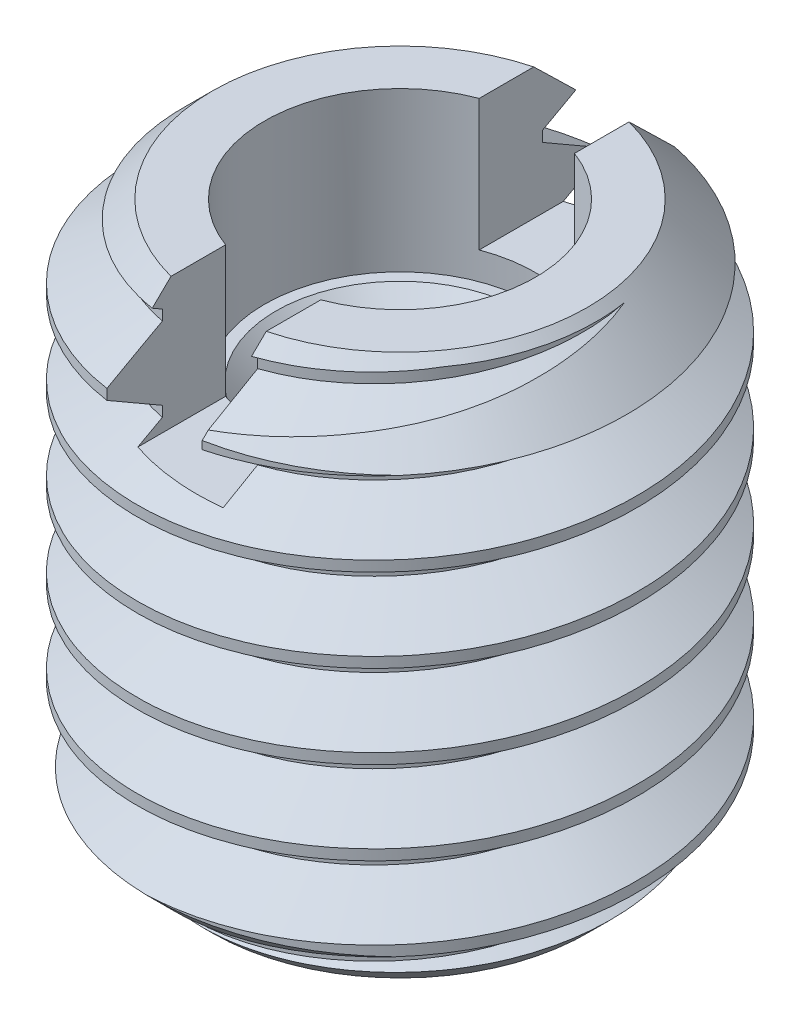
SolidWorks part; units mm, degrees
ref_plane "Front Plane" through (0, 0, 0) normal (0, 0, 1) x (1, 0, 0)
ref_plane "Top Plane" through (0, 0, 0) normal (0, 1, 0) x (1, 0, 0)
ref_plane "Right Plane" through (0, 0, 0) normal (1, 0, 0) x (0, 0, -1)
sketch "Sketch1" plane through (0, 0, 0) normal (0, 1, 0) x (1, 0, 0)
  line L0 (-3, 0) -> (3, 0) construction
  circle A0 centre (0, 0) radius 3
  dimension "External Thread OD" = 6
extrude "Extrude1" add sketch "Sketch1" against normal blind 6.5024
sketch "Sketch4" plane through (0, 0, 0) normal (0, 1, 0) x (1, 0, 0)
  circle A2 centre (0, 0) radius 1.5
  point P0 (-1.5, 0)
  dimension "Internal Thread OD" = 3
sketch "Sketch2" plane through (0, 0, 0) normal (0, 1, 0) x (1, 0, 0)
  circle A0 centre (0, 0) radius 1.6256
  dimension "A" = 3.2512
extrude "Extrude2" cut sketch "Sketch2" against normal blind 1.905
sketch "Sketch3" plane through (0, 0, 0) normal (0, 0, 1) x (1, 0, 0)
  line L5 (-0.5715, 0) -> (0.5715, 0)
  line L6 (-0.5715, 0) -> (-0.5715, -1.5748)
  line L7 (-0.5715, -1.5748) -> (0.5715, -1.5748)
  line L8 (0.5715, 0) -> (0.5715, -1.5748)
  dimension "B" = 1.143
  dimension "C" = 1.5748
extrude "Extrude3" cut sketch "Sketch3" along normal through all and the other way through all
curve "Helix/Spiral1" pitch 0.5 height 7.0024 radius 1.5 centre (0, 0, 0) axis (0, -1, 0) start towards (0, 0, 1) parameters "Internal Thread Height"=7.0024, "Internal Thread Pitch"=0.5
sketch "Sketch5" plane through (0, 0, 0) normal (0, 0, 1) x (1, 0, 0)
  line L0 (-1.1211, 0.4688) -> (-1.1211, -0.0312) construction
  line L1 (-1.1211, -0.0312) -> (-1.5541, 0.2188) construction
  line L2 (-1.5541, 0.2188) -> (-1.1211, 0.4688) construction
  line L3 (-1.1211, 0.2188) -> (-1.1752, 0.2188) construction
  line L4 (-1.1752, 0.2188) -> (-1.4459, 0.2188) construction
  line L5 (-1.5, 0.2188) -> (-1.5541, 0.2188) construction
  line L6 (-1.5, 0.25) -> (-1.5, 0.1875) construction
  line L7 (-1.1752, 0) -> (-1.1752, 0.4375) construction
  line L8 (-1.5, 0.1875) -> (-1.5, 0) construction
  line L9 (-1.5, 0) -> (-1.1752, 0) construction
  line L10 (-1.4459, 0.2813) -> (-1.4459, 0.1563)
  line L11 (-1.4459, 0.1563) -> (-1.1482, -0.0156)
  line L12 (-1.1482, -0.0156) -> (-1.1482, 0.4531)
  line L13 (-1.1482, 0.4531) -> (-1.4459, 0.2813)
  line L14 (-1.5, 0.2188) -> (-1.4459, 0.2188) construction
  point P18 (-1.1482, 0.2188)
  dimension "D1" = 0.5
  dimension "D2" = 0.0625
sketch "Sketch6" plane through (0, 0, 0) normal (0, 1, 0) x (-1, 0, 0)
  circle A0 centre (0, 0) radius 1.1752
extrude "Extrude4" cut sketch "Sketch6" against normal through all
chamfer "Chamfer1" distance 0.3125 angle 45 2 edges at (0, -6.5024, 1.1752) (0, -1.905, 1.1752)
sweep "Cut-Sweep1" cut profiles "Sketch5" path "Helix/Spiral1" align with end faces yes
sketch "Sketch7" plane through (0, 0, 0) normal (0, 1, 0) x (1, 0, 0)
  circle A0 centre (0, 0) radius 3 construction
  circle A1 centre (0, 0) radius 3
  point P3 (-3, 0)
curve "Helix/Spiral2" pitch 1 height 7.0024 radius 3 centre (0, 0, 0) axis (0, -1, 0) start towards (0, 0, 1) parameters "External Thread Height"=7.0024, "External Thread Pitch"=1
sketch "Sketch8" plane through (0, 0, 0) normal (0, 0, 1) x (1, 0, 0)
  line L0 (-3.1083, 0.9375) -> (-3.1083, -0.0625) construction
  line L1 (-3.1083, 0.9375) -> (-2.2422, 0.4375) construction
  line L2 (-2.2422, 0.4375) -> (-3.1083, -0.0625) construction
  line L3 (-3, 0.875) -> (-3, 0) construction
  line L4 (-2.3505, 0.5) -> (-2.3505, 0.375)
  line L5 (-3.0541, 0.9063) -> (-2.3505, 0.5)
  line L6 (-3.0541, 0.9063) -> (-3.0541, -0.0313)
  line L7 (-3.0541, -0.0313) -> (-2.3505, 0.375)
  line L8 (-3.1083, 0.4375) -> (-3, 0.4375) construction
  line L9 (-2.3505, 0.4375) -> (-2.2422, 0.4375) construction
  point P13 (-3.0541, 0.4375)
  dimension "D1" = 1
  dimension "D2" = 0.125
chamfer "Chamfer2" distance 0.75 angle 45 3 edges at (0, -6.5024, 3) (3, 0, 0) (-3, 0, 0)
sweep "Cut-Sweep2" cut profiles "Sketch8" path "Helix/Spiral2" align with end faces yes
equation "\"Internal Thread Height@Helix/Spiral1\" = \"Internal Thread Pitch@Helix/Spiral1\" + \"Length@Extrude1\""
equation "\"D1@Sketch5\" = \"Internal Thread Pitch@Helix/Spiral1\""
equation "\"D2@Sketch5\" = \"D1@Sketch5\" / 8"
equation "\"D1@Chamfer1\" = \"Internal Thread Pitch@Helix/Spiral1\" * 5 / 8"
equation "\"External Thread Height@Helix/Spiral2\" = \"Internal Thread Height@Helix/Spiral1\""
equation "\"D1@Sketch8\" = \"External Thread Pitch@Helix/Spiral2\""
equation "\"D2@Sketch8\" = \"D1@Sketch8\" / 8"
equation "\"D1@Chamfer2\" = \"External Thread Pitch@Helix/Spiral2\" * 6 / 8"
